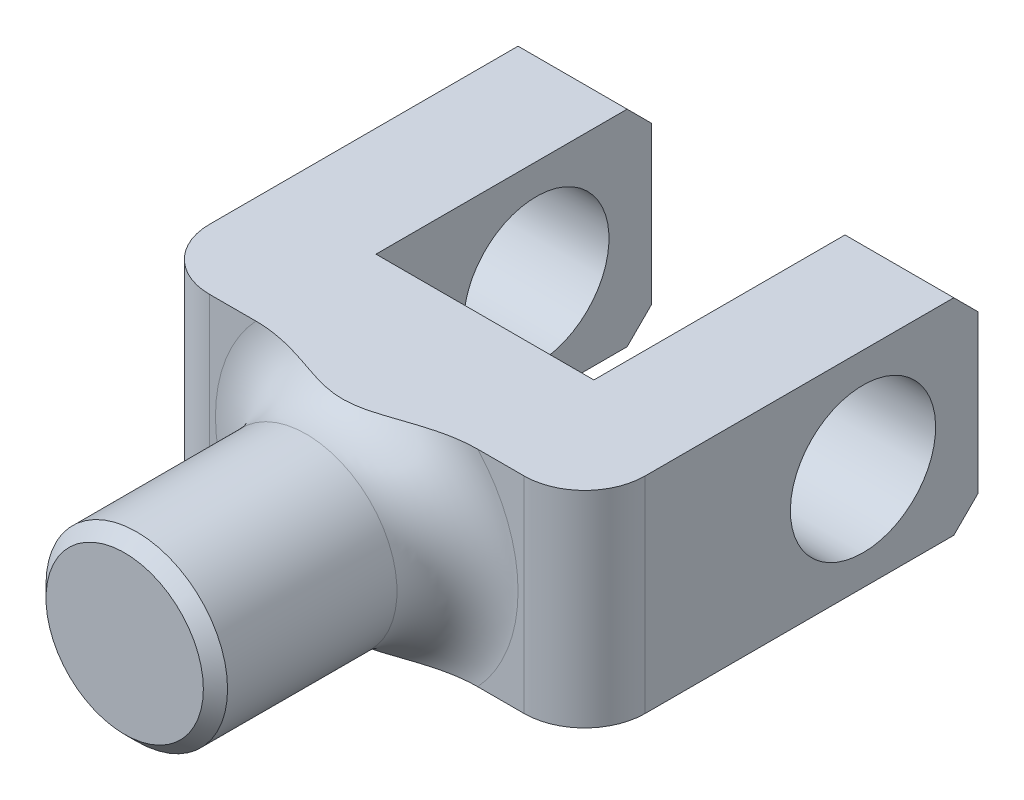
SolidWorks part; units mm, degrees
ref_plane "Płaszczyzna przednia" through (0, 0, 0) normal (0, 0, 1) x (1, 0, 0)
ref_plane "Płaszczyzna górna" through (0, 0, 0) normal (0, 1, 0) x (1, 0, 0)
ref_plane "Płaszczyzna prawa" through (0, 0, 0) normal (1, 0, 0) x (0, 0, -1)
sketch "Szkic1" plane through (0, 0, 0) normal (0, 0, 1) x (1, 0, 0)
  line L0 (-44.7709, 40.3158) -> (27.2291, 40.3158)
  line L1 (27.2291, 40.3158) -> (27.2291, 6.3158)
  line L2 (27.2291, 6.3158) -> (-44.7709, 6.3158)
  line L3 (-44.7709, 6.3158) -> (-44.7709, 40.3158)
  dimension "D1" = 72
  dimension "D2" = 34
extrude "Dodanie-wyciągnięcie1" add sketch "Szkic1" along normal blind 65
ref_point "Punkt1"
sketch "Szkic3" plane through (0, 0, 65) normal (0, 0, 1) x (1, 0, 0)
  circle A0 centre (-8.7709, 23.3158) radius 15
extrude "Dodanie-wyciągnięcie2" add sketch "Szkic3" along normal blind 40
cosmetic thread "Oznaczenie gwintu2" parameters "D1"=25, "D2"=26.158
sketch "Szkic4" plane through (0, 0, 0) normal (0, 0, -1) x (-1, 0, 0)
  line L2 (-27.2291, 40.3158) -> (44.7709, 40.3158) construction
  line L4 (-9.2555, 40.3158) -> (-9.2555, 6.3158)
  line L5 (44.7709, 6.3158) -> (-27.2291, 6.3158) construction
  line L6 (-9.2555, 6.3158) -> (26.7445, 6.3158)
  line L7 (26.7445, 6.3158) -> (26.7445, 40.3158)
  line L8 (26.7445, 40.3158) -> (-9.2555, 40.3158)
  dimension "D1" = 36
extrude "Wytnij-wyciągnięcie1" cut sketch "Szkic4" against normal blind 45.5
sketch "Szkic5" plane through (-44.7709, 0, 0) normal (-1, 0, 0) x (0, 0, 1)
  line L0 (0, 6.3158) -> (19, 6.3158)
  line L1 (65, 6.3158) -> (0, 6.3158) construction
  line L2 (19, 6.3158) -> (19, 40.3158)
  line L3 (65, 40.3158) -> (0, 40.3158) construction
  dimension "D1" = 19
sketch "Szkic6" plane through (-44.7709, 0, 0) normal (-1, 0, 0) x (0, 0, 1)
  line L0 (19, 6.3158) -> (19, 40.3158) construction
  circle A0 centre (19, 23.3158) radius 12
extrude "Wytnij-wyciągnięcie2" cut sketch "Szkic6" against normal blind 73
fillet "Zaokrąglenie1" radius 10 1 edges at (6.2291, 23.3158, 65) type face fillet first side face at (6.2291, 23.3158, 105) second side face at (6.2291, 23.3158, 65)
fillet "Zaokrąglenie2" radius 10 1 edges at (-44.7709, 23.3158, 65) type face fillet first side face at (-44.7709, 23.3158, 31) second side face at (-37.6035, 23.3158, 65)
fillet "Zaokrąglenie3" radius 10 1 edges at (27.2291, 23.3158, 65) type face fillet first side face at (27.2291, 11.3158, 19) second side face at (20.0617, 23.3158, 65)
ref_point "Point2"
chamfer "Chamfer4" distance 4 angle 45 1 edges at (18.2423, 40.3158, 0)
chamfer "Chamfer5" distance 4 angle 45 3 edges at (18.2423, 6.3158, 0) (-35.7577, 6.3158, 0) (-35.7577, 40.3158, 0)
chamfer "Chamfer6" distance 2 angle 45 1 edges at (6.2291, 23.3158, 105)
